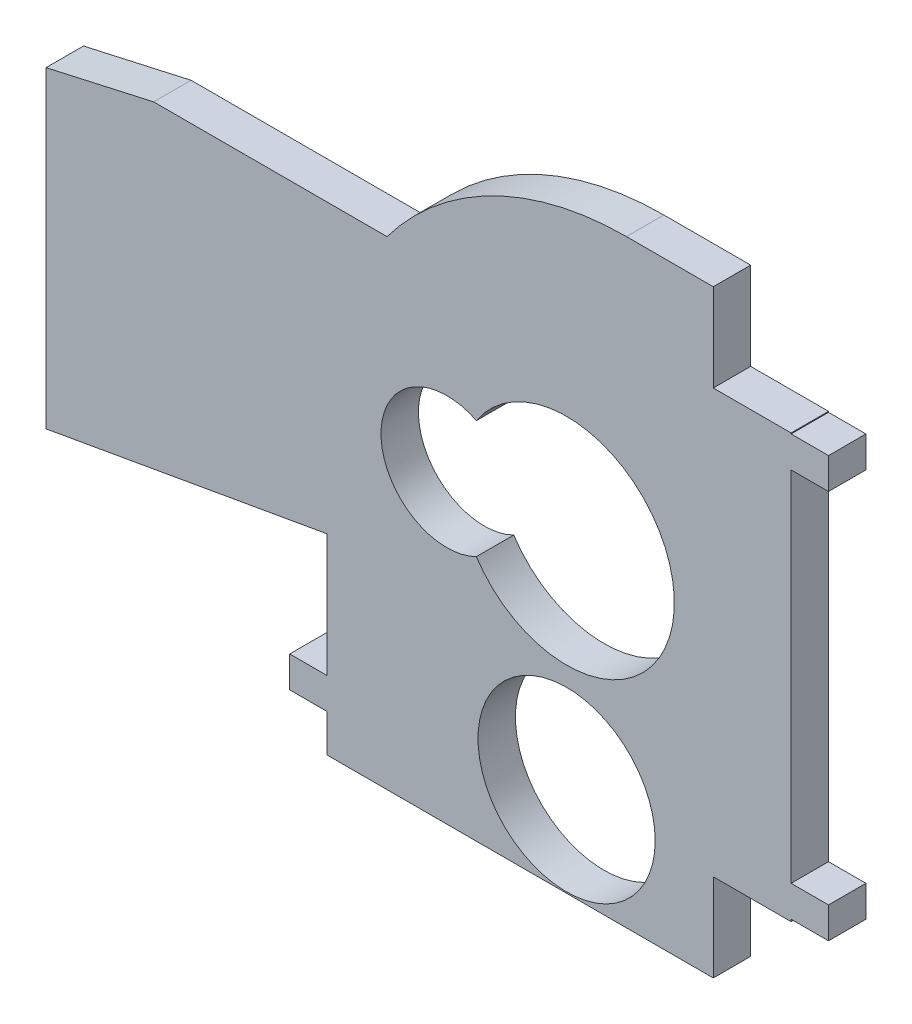
SolidWorks part; units mm, degrees
material "Balsa"
ref_plane "Front Plane" through (0, 0, 0) normal (0, 0, 1) x (1, 0, 0)
ref_plane "Top Plane" through (0, 0, 0) normal (0, 1, 0) x (1, 0, 0)
ref_plane "Right Plane" through (0, 0, 0) normal (1, 0, 0) x (0, 0, -1)
sketch "Sketch1" plane through (0, 0, 0) normal (0, 0, 1) x (1, 0, 0)
  line L0 (0, -1000.1535) -> (0, 48999.8465) construction
  line L1 (0, 9.144) -> (-5.08, 9.144) construction
  line L2 (-1000, 0) -> (49000, 0) construction
  line L3 (9.525, 16.51) -> (11.1125, 16.51)
  line L4 (2.54, 21.59) -> (9.525, 21.59)
  line L5 (-10.16, 8.89) -> (-10.16, -3.81)
  line L6 (-10.16, -3.81) -> (9.525, -3.81)
  line L7 (9.525, 21.59) -> (9.525, -3.81)
  line L8 (-11.7475, -2.2098) -> (-10.16, -2.2098)
  line L9 (-11.7475, -2.2098) -> (-11.7475, -0.889)
  line L10 (-11.7475, -0.889) -> (-10.16, -0.889)
  line L11 (-10.16, -2.2098) -> (-10.16, -0.889)
  line L12 (9.525, 0) -> (11.1125, 0)
  line L13 (9.525, 0) -> (9.525, 1.3208)
  line L14 (9.525, 1.3208) -> (11.1125, 1.3208)
  line L15 (11.1125, 0) -> (11.1125, 1.3208)
  line L16 (9.525, 16.51) -> (9.525, 17.8308)
  line L17 (9.525, 17.8308) -> (11.1125, 17.8308)
  line L18 (11.1125, 16.51) -> (11.1125, 17.8308)
  line L19 (-7.62, 16.51) -> (-22.0849, 16.51)
  line L21 (-22.0849, 2.212) -> (-10.16, 4.318)
  line L22 (9.525, 8.89) -> (-35.5862, 8.89) construction
  line L27 (-22.0849, 13.081) -> (-22.0849, 4.699)
  line L29 (-22.0849, 15.487) -> (-17.5195, 16.51)
  line L30 (-22.0849, 13.081) -> (-22.0849, 15.487)
  line L31 (9.525, 12.7762) -> (9.525, 4.9022)
  line L32 (-22.0849, 4.699) -> (-22.0849, 2.212)
  line L33 (-22.0849, 15.487) -> (-22.0849, 16.51)
  circle A0 centre (0, 0) radius 3.7592
  arc A1 (-3.829, 6.6457) -> (-3.829, 11.6423) centre (0, 9.144) ccw
  arc A2 (-3.829, 11.6423) -> (-3.829, 6.6457) centre (-5.08, 9.144) ccw
  arc A3 (2.54, 21.59) -> (-10.16, 8.89) centre (2.54, 8.89) ccw
  point P33 (9.525, 8.89)
  point P35 (-27.4189, 8.89)
  dimension "D1" = 7.5184
  dimension "D4" = 3.81
  dimension "D3" = 9.144
  dimension "D5" = 2.794
  dimension "D9" = 12.7
  dimension "D10" = 1.5875
  dimension "D2" = 25.4
  dimension "D6" = 9.525
  dimension "D7" = 5.08
  dimension "D8" = 19.685
  dimension "D11" = 9.144
  dimension "D12" = 1.3208
  dimension "D13" = 1.3208
  dimension "D14" = 1.5875
  dimension "D15" = 2
  dimension "D16" = 8.128
  dimension "D17" = 5.207
  dimension "D19" = 8.382
  dimension "D21" = 14.4649
  dimension "D22" = 5.08
extrude "Boss-Extrude1" add sketch "Sketch1" along normal blind 1.5875 contours L4 A3 L5 L6 L7 A0 A2 A1 | L10 L9 L8 L5 | L3 L18 L17 L7 | L12 L15 L14 L7 | A3 L19 L21 L5 | L21 region at (10.3187, 17.1704, 0) region at (9.2036, 14.6431, 0) region at (10.3187, 0.6604, 0) region at (-15.9568, 9.9646, 0) region at (-10.9538, -1.5494, 0)
sketch "Sketch2" plane through (0, 0, 1.5875) normal (0, 0, 1) x (1, 0, 0)
  line L1 (6.223, -3.8481) -> (9.525, -3.8481)
  line L2 (6.223, -3.8481) -> (6.223, -0.0889)
  line L3 (6.223, -0.0889) -> (9.525, -0.0889)
  line L4 (9.525, -3.8481) -> (9.525, -0.0889)
  line L5 (9.525, -0.9144) -> (9.525, -3.0226)
  line L7 (9.525, 20.8026) -> (9.525, 18.6944)
  line L9 (6.223, 17.8689) -> (9.525, 17.8689)
  line L10 (6.223, 17.8689) -> (6.223, 21.6281)
  line L11 (6.223, 21.6281) -> (9.525, 21.6281)
  line L12 (9.525, 17.8689) -> (9.525, 21.6281)
  point P8 (9.525, -1.9685)
  point P9 (9.525, -1.9685)
  point P10 (9.525, 19.7485)
  point P15 (9.525, 19.7485)
  line M4 (9.525, 21.59) -> (2.54, 21.59)
  line M11 (-10.16, -3.81) -> (9.525, -3.81)
  line M12 (9.525, -3.81) -> (9.525, 0)
  line M20 (9.525, 17.8308) -> (9.525, 21.59)
  dimension "D1" = 3.7592
  dimension "D2" = 3.302
  dimension "D3" = 3.7592
  dimension "D4" = 3.302
extrude "Cut-Extrude1" cut sketch "Sketch2" against normal up to next contours L3 L2 L4 M11 M12 | L10 L9 M20 M4 region at (7.874, -1.9495, 1.5875) region at (7.874, 19.7294, 1.5875)
move or copy body "Body-Move/Copy1" [suppressed] bodies to move or copy 102
